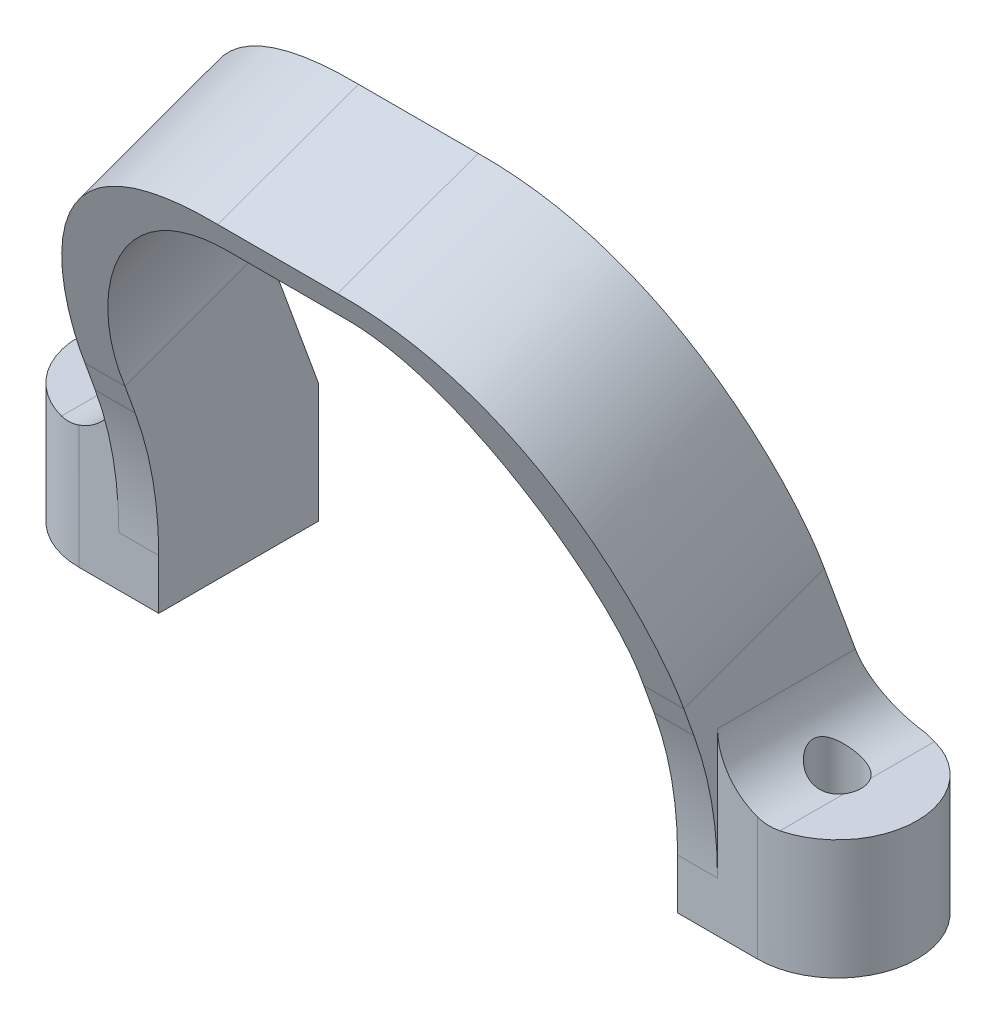
SolidWorks part; units mm, degrees
ref_plane "Спереди" through (0, 0, 0) normal (0, 0, 1) x (1, 0, 0)
ref_plane "Сверху" through (0, 0, 0) normal (0, 1, 0) x (1, 0, 0)
ref_plane "Справа" through (0, 0, 0) normal (1, 0, 0) x (0, 0, -1)
sketch "Эскиз1" plane through (0, 0, 0) normal (0, 1, 0) x (1, 0, 0)
  line L0 (-30.143, 4) -> (-26.143, 4)
  line L1 (-26.143, 4) -> (-26.143, -4)
  line L2 (-26.143, -4) -> (-30.143, -4)
  line L3 (3.857, 4) -> (-0.143, 4)
  line L4 (-0.143, 4) -> (-0.143, -4)
  line L5 (-0.143, -4) -> (3.857, -4)
  arc A0 (-30.143, 4) -> (-30.143, -4) centre (-30.143, 0) ccw
  arc A1 (3.857, -4) -> (3.857, 4) centre (3.857, 0) ccw
  circle A2 centre (-30.143, 0) radius 1.2
  circle A3 centre (3.857, 0) radius 1.2
  dimension "D1" = 34
extrude "Бобышка-Вытянуть1" add sketch "Эскиз1" along normal blind 6
sketch "Эскиз3" plane through (-26.143, 0, 0) normal (1, 0, 0) x (0, 0, -1)
  line L0 (0, 6) -> (0, 15) construction
  line L3 (0, 15) -> (-4.4463, 27.216) construction
  line L4 (-4.4463, 27.216) -> (-17.1497, 22.5923) construction
  line L5 (0, 6) -> (-7.3388, 26.1632) construction
  line L6 (-4, 6) -> (-5.6919, 10.705)
  line L7 (4, 6) -> (1.3541, 13.2696)
  line L8 (4, 6) -> (-4, 6) construction
  line L9 (4, 0) -> (-4, 0) construction
  line L10 (-4, 0) -> (4, 0)
  line L11 (4, 0) -> (4, 6)
  line L12 (-4, 6) -> (-5.6919, 10.705)
  line L13 (-5.6919, 10.705) -> (1.3541, 13.2696)
  line M9 (4, 6) -> (-4, 6)
  dimension "D1" = 160
extrude "Бобышка-Вытянуть3" add sketch "Эскиз3" against normal blind 2 contours L13 L6 L7 M9 region at (-26.143, 9.0379, 0.8149)
sketch "Эскиз5" plane through (-0.143, 0, 0) normal (-1, 0, 0) x (0, 0, 1)
  line L0 (-4, 6) -> (-1.3541, 13.2696)
  line L1 (-1.3541, 13.2696) -> (5.6919, 10.705)
  line L2 (5.6919, 10.705) -> (4, 6)
  line L3 (-4, 6) -> (-4, 0)
  line L4 (-4, 0) -> (4, 0)
  line L5 (4, 0) -> (-4, 0) construction
  line L6 (4, 0) -> (4, 6)
extrude "Бобышка-Вытянуть4" add sketch "Эскиз5" against normal blind 2
fillet "Скругление3" radius 20 1 edges
fillet "Скругление4" radius 20 1 edges at (0.857, 6, 4)
sketch "Эскиз6" plane through (0, 1.9874, -5.4605) normal (0, 0.342, -0.9397) x (-1, 0, 0)
  line L0 (-3.857, 5.6382) -> (30.143, 5.6382) construction
  line L1 (13.143, 5.6382) -> (13.143, 27.6382) construction
  line L2 (16.143, 27.6382) -> (10.143, 27.6382)
  line L3 (13.143, 27.6382) -> (13.143, 26.1382) construction
  line L4 (10.143, 27.6382) -> (10.143, 26.1382)
  line L5 (10.143, 26.1382) -> (16.143, 26.1382)
  line L6 (16.143, 27.6382) -> (16.143, 26.1382)
  line L7 (-1.857, 12.0062) -> (0.143, 12.0062)
  line L8 (26.143, 12.0062) -> (28.143, 12.0062)
  line L9 (-3.857, -1.3681) -> (0.143, -1.3681) construction
  spline S0 degree 3 poles (10.143, 27.6382) (0.0892, 27.8429) (-1.9686, 15.7064) (-1.857, 12.0062) knots 0 0 0 0 1 1 1 1
  spline S1 degree 3 poles (0.143, 12.0062) (-0.1289, 16.9452) (4.2526, 26.119) (10.143, 26.1382) knots 0 0 0 0 1 1 1 1
  spline S2 degree 3 poles (26.143, 12.0062) (26.415, 16.9452) (22.0334, 26.119) (16.143, 26.1382) knots 0 0 0 0 1 1 1 1
  spline S3 degree 3 poles (16.143, 27.6382) (26.1968, 27.8429) (28.2547, 15.7064) (28.143, 12.0062) knots 0 0 0 0 1 1 1 1
  line M2 (0.143, 12.0062) -> (-1.857, 12.0062)
  dimension "D1" = 22
  dimension "D2" = 1.5
  dimension "D3" = 7.0062
extrude "Бобышка-Вытянуть5" add sketch "Эскиз6" against normal up to vertex (7.4982 mm away) contours S1 L4 S0 M2 | L6 L2 L4 L5 | S3 L6 S2 L8 region at (-13.143, 27.254, 3.7358) region at (-23.6887, 21.6274, 1.6879) region at (-2.5974, 21.6274, 1.6879) up to point (1.857, 10.705, 5.6919)
fillet "Скругление5" radius 3 2 edges at (1.857, 6, 0)
